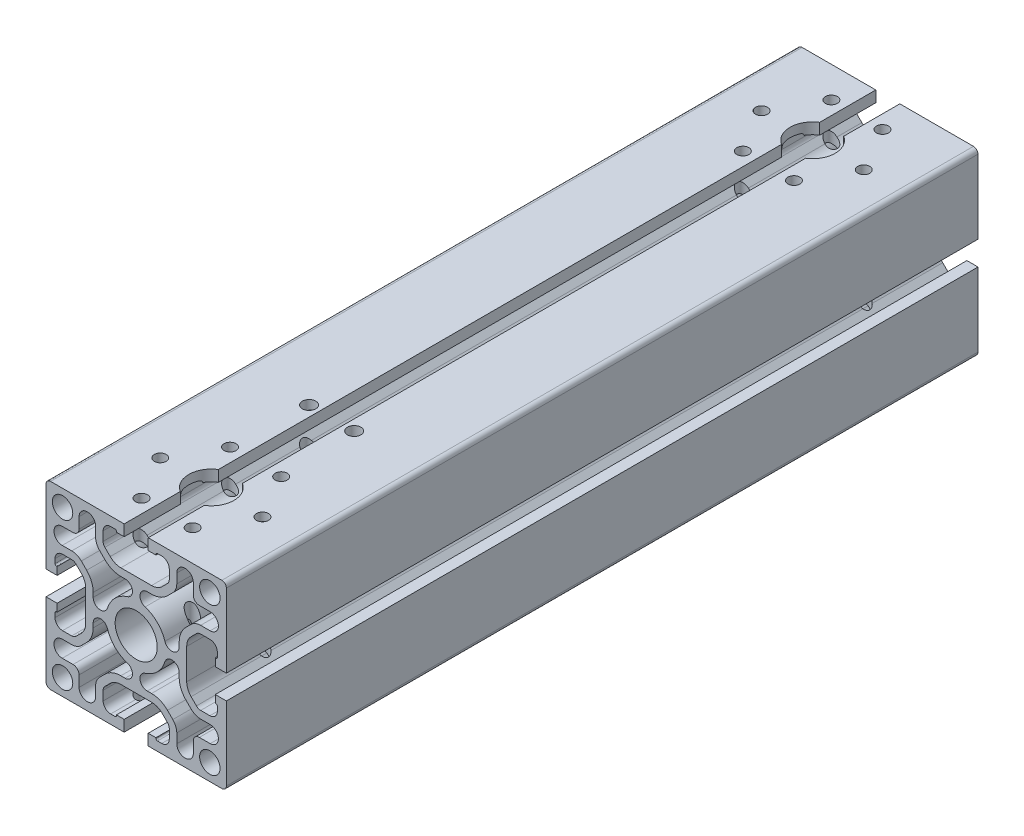
SolidWorks part; units mm, degrees
ref_plane "Płaszczyzna przednia" through (0, 0, 0) normal (0, 0, 1) x (1, 0, 0)
ref_plane "Płaszczyzna górna" through (0, 0, 0) normal (0, 1, 0) x (1, 0, 0)
ref_plane "Płaszczyzna prawa" through (0, 0, 0) normal (1, 0, 0) x (0, 0, -1)
ref_plane "Plane1" through (0, 0, 0) normal (0, 0, -1) x (-1, 0, 0)
sketch "Sketch1" plane through (0, 0, 0) normal (0, 0, -1) x (-1, 0, 0)
  line L0 (5.1034, -14.3) -> (3.6784, -14.3)
  line L1 (14.3, -3.6784) -> (14.3, -5.1134)
  line L2 (16.4818, -10.4017) -> (18.2431, -12.173)
  line L3 (21.434, -13.5) -> (24.6, -13.5)
  line L4 (24.6, -19) -> (21, -19)
  line L5 (19, -21) -> (19, -24.6)
  line L6 (13.5, -24.6) -> (13.5, -21.454)
  line L7 (12.182, -18.272) -> (10.4067, -16.4967)
  line L8 (-3.6784, -14.3) -> (-5.1034, -14.3)
  line L9 (-10.4067, -16.4967) -> (-12.182, -18.272)
  line L10 (-13.5, -21.454) -> (-13.5, -24.6)
  line L11 (-19, -24.6) -> (-19, -21)
  line L12 (-21, -19) -> (-24.6, -19)
  line L13 (-24.6, -13.5) -> (-21.434, -13.5)
  line L14 (-18.2431, -12.173) -> (-16.4818, -10.4017)
  line L15 (-14.3, -5.1134) -> (-14.3, -3.6784)
  line L16 (-5.1034, 14.3) -> (-3.6784, 14.3)
  line L17 (-14.3, 3.6784) -> (-14.3, 5.1134)
  line L18 (-16.4818, 10.4017) -> (-18.2431, 12.173)
  line L19 (-21.434, 13.5) -> (-24.6, 13.5)
  line L20 (-24.6, 19) -> (-21, 19)
  line L21 (-19, 21) -> (-19, 24.6)
  line L22 (-13.5, 24.6) -> (-13.5, 21.454)
  line L23 (-12.182, 18.272) -> (-10.4067, 16.4967)
  line L24 (3.6784, 14.3) -> (5.1034, 14.3)
  line L25 (10.4067, 16.4967) -> (12.182, 18.272)
  line L26 (13.5, 21.454) -> (13.5, 24.6)
  line L27 (19, 24.6) -> (19, 21)
  line L28 (21, 19) -> (24.6, 19)
  line L29 (24.6, 13.5) -> (21.434, 13.5)
  line L30 (18.2431, 12.173) -> (16.4818, 10.4017)
  line L31 (14.3, 5.1134) -> (14.3, 3.6784)
  line L32 (5.1, 16.8) -> (-5.11, 16.8)
  line L33 (-8.6455, 18.2645) -> (-10.42, 20.04)
  line L34 (-11, 21.45) -> (-11, 24.5)
  line L35 (-8.5, 27) -> (-7.07, 27)
  line L36 (-6.57, 26.5) -> (-6.57, 26.3)
  line L37 (-6.57, 26.3) -> (-4, 26.3)
  line L38 (-4, 26.3) -> (-4, 30)
  line L39 (-4, 30) -> (-28.5, 30)
  line L40 (-30, 28.5) -> (-30, 4)
  line L41 (-30, 4) -> (-26.3, 4)
  line L42 (-26.3, 4) -> (-26.3, 6.57)
  line L43 (-26.3, 6.57) -> (-26.5, 6.57)
  line L44 (-27, 7.07) -> (-27, 8.5)
  line L45 (-24.5, 11) -> (-21.45, 11)
  line L46 (-20.0358, 10.4142) -> (-18.27, 8.65)
  line L47 (-16.8, 5.11) -> (-16.8, -5.1)
  line L48 (-18.2645, -8.6355) -> (-20.04, -10.41)
  line L49 (-21.45, -11) -> (-24.5, -11)
  line L50 (-27, -8.5) -> (-27, -7.07)
  line L51 (-26.5, -6.57) -> (-26.3, -6.57)
  line L52 (-26.3, -6.57) -> (-26.3, -4)
  line L53 (-26.3, -4) -> (-30, -4)
  line L54 (-30, -4) -> (-30, -28.5)
  line L55 (-28.5, -30) -> (-4, -30)
  line L56 (-4, -30) -> (-4, -26.3)
  line L57 (-4, -26.3) -> (-6.57, -26.3)
  line L58 (-6.57, -26.3) -> (-6.57, -26.5)
  line L59 (-7.07, -27) -> (-8.5, -27)
  line L60 (-11, -24.5) -> (-11, -21.45)
  line L61 (-10.4142, -20.0358) -> (-8.65, -18.26)
  line L62 (-5.11, -16.8) -> (5.1, -16.8)
  line L63 (8.64, -18.26) -> (10.41, -20.03)
  line L64 (11, -21.45) -> (11, -24.5)
  line L65 (8.5, -27) -> (7.07, -27)
  line L66 (6.57, -26.5) -> (6.57, -26.3)
  line L67 (6.57, -26.3) -> (4, -26.3)
  line L68 (4, -26.3) -> (4, -30)
  line L69 (4, -30) -> (28.5, -30)
  line L70 (30, -28.5) -> (30, -4)
  line L71 (30, -4) -> (26.3, -4)
  line L72 (26.3, -4) -> (26.3, -6.57)
  line L73 (26.3, -6.57) -> (26.5, -6.57)
  line L74 (27, -7.07) -> (27, -8.5)
  line L75 (24.5, -11) -> (21.45, -11)
  line L76 (20.0358, -10.4142) -> (18.26, -8.64)
  line L77 (16.8, -5.1) -> (16.8, 5.11)
  line L78 (18.26, 8.65) -> (20.0358, 10.4142)
  line L79 (21.45, 11) -> (24.5, 11)
  line L80 (27, 8.5) -> (27, 7.07)
  line L81 (26.5, 6.57) -> (26.3, 6.57)
  line L82 (26.3, 6.57) -> (26.3, 4)
  line L83 (26.3, 4) -> (30, 4)
  line L84 (30, 4) -> (30, 28.5)
  line L85 (28.5, 30) -> (4, 30)
  line L86 (4, 30) -> (4, 26.3)
  line L87 (4, 26.3) -> (6.57, 26.3)
  line L88 (6.57, 26.3) -> (6.57, 26.5)
  line L89 (7.07, 27) -> (8.5, 27)
  line L90 (11, 24.5) -> (11, 21.45)
  line L91 (10.4142, 20.0358) -> (8.64, 18.27)
  circle A0 centre (-24.5, 24.5) radius 3.4
  circle A1 centre (24.5, 24.5) radius 3.4
  circle A2 centre (-24.5, -24.49) radius 3.4
  circle A3 centre (24.5, -24.49) radius 3.4
  circle A4 centre (0, 0) radius 7
  arc A5 (3.6784, -14.3) -> (2.9597, -9.552) centre (3.6784, -11.8716) cw
  arc A6 (2.9597, -9.552) -> (9.552, -2.9597) centre (0, 0) ccw
  arc A7 (9.552, -2.9597) -> (14.3, -3.6784) centre (11.8716, -3.6784) cw
  arc A8 (14.3, -5.1134) -> (16.4818, -10.4017) centre (21.8, -5.1134) ccw
  arc A9 (18.2431, -12.173) -> (21.434, -13.5) centre (21.434, -9) ccw
  arc A10 (24.6, -13.5) -> (24.6, -19) centre (24.6, -16.25) cw
  arc A11 (21, -19) -> (19, -21) centre (21, -21) ccw
  arc A12 (19, -24.6) -> (13.5, -24.6) centre (16.25, -24.6) cw
  arc A13 (13.5, -21.454) -> (12.182, -18.272) centre (9, -21.454) ccw
  arc A14 (10.4067, -16.4967) -> (5.1034, -14.3) centre (5.1034, -21.8) ccw
  arc A15 (-9.552, -2.9597) -> (-2.9597, -9.552) centre (0, 0) ccw
  arc A16 (-2.9597, -9.552) -> (-3.6784, -14.3) centre (-3.6784, -11.8716) cw
  arc A17 (-5.1034, -14.3) -> (-10.4067, -16.4967) centre (-5.1034, -21.8) ccw
  arc A18 (-12.182, -18.272) -> (-13.5, -21.454) centre (-9, -21.454) ccw
  arc A19 (-13.5, -24.6) -> (-19, -24.6) centre (-16.25, -24.6) cw
  arc A20 (-19, -21) -> (-21, -19) centre (-21, -21) ccw
  arc A21 (-24.6, -19) -> (-24.6, -13.5) centre (-24.6, -16.25) cw
  arc A22 (-21.434, -13.5) -> (-18.2431, -12.173) centre (-21.434, -9) ccw
  arc A23 (-16.4818, -10.4017) -> (-14.3, -5.1134) centre (-21.8, -5.1134) ccw
  arc A24 (-14.3, -3.6784) -> (-9.552, -2.9597) centre (-11.8716, -3.6784) cw
  arc A25 (-3.6784, 14.3) -> (-2.9597, 9.552) centre (-3.6784, 11.8716) cw
  arc A26 (-2.9597, 9.552) -> (-9.552, 2.9597) centre (0, 0) ccw
  arc A27 (-9.552, 2.9597) -> (-14.3, 3.6784) centre (-11.8716, 3.6784) cw
  arc A28 (-14.3, 5.1134) -> (-16.4818, 10.4017) centre (-21.8, 5.1134) ccw
  arc A29 (-18.2431, 12.173) -> (-21.434, 13.5) centre (-21.434, 9) ccw
  arc A30 (-24.6, 13.5) -> (-24.6, 19) centre (-24.6, 16.25) cw
  arc A31 (-21, 19) -> (-19, 21) centre (-21, 21) ccw
  arc A32 (-19, 24.6) -> (-13.5, 24.6) centre (-16.25, 24.6) cw
  arc A33 (-13.5, 21.454) -> (-12.182, 18.272) centre (-9, 21.454) ccw
  arc A34 (-10.4067, 16.4967) -> (-5.1034, 14.3) centre (-5.1034, 21.8) ccw
  arc A35 (9.552, 2.9597) -> (2.9597, 9.552) centre (0, 0) ccw
  arc A36 (2.9597, 9.552) -> (3.6784, 14.3) centre (3.6784, 11.8716) cw
  arc A37 (5.1034, 14.3) -> (10.4067, 16.4967) centre (5.1034, 21.8) ccw
  arc A38 (12.182, 18.272) -> (13.5, 21.454) centre (9, 21.454) ccw
  arc A39 (13.5, 24.6) -> (19, 24.6) centre (16.25, 24.6) cw
  arc A40 (19, 21) -> (21, 19) centre (21, 21) ccw
  arc A41 (24.6, 19) -> (24.6, 13.5) centre (24.6, 16.25) cw
  arc A42 (21.434, 13.5) -> (18.2431, 12.173) centre (21.434, 9) ccw
  arc A43 (16.4818, 10.4017) -> (14.3, 5.1134) centre (21.8, 5.1134) ccw
  arc A44 (14.3, 3.6784) -> (9.552, 2.9597) centre (11.8716, 3.6784) cw
  arc A45 (-5.11, 16.8) -> (-8.6455, 18.2645) centre (-5.11, 21.8) cw
  arc A46 (-10.42, 20.04) -> (-11, 21.45) centre (-8.9925, 21.4515) cw
  arc A47 (-11, 24.5) -> (-8.5, 27) centre (-8.5, 24.5) cw
  arc A48 (-7.07, 27) -> (-6.57, 26.5) centre (-7.07, 26.5) cw
  arc A49 (-28.5, 30) -> (-30, 28.5) centre (-28.5, 28.5) ccw
  arc A50 (-26.5, 6.57) -> (-27, 7.07) centre (-26.5, 7.07) cw
  arc A51 (-27, 8.5) -> (-24.5, 11) centre (-24.5, 8.5) cw
  arc A52 (-21.45, 11) -> (-20.0358, 10.4142) centre (-21.45, 9) cw
  arc A53 (-18.27, 8.65) -> (-16.8, 5.11) centre (-21.7951, 5.111) cw
  arc A54 (-16.8, -5.1) -> (-18.2645, -8.6355) centre (-21.8, -5.1) cw
  arc A55 (-20.04, -10.41) -> (-21.45, -11) centre (-21.4424, -9.0384) cw
  arc A56 (-24.5, -11) -> (-27, -8.5) centre (-24.5, -8.5) cw
  arc A57 (-27, -7.07) -> (-26.5, -6.57) centre (-26.5, -7.07) cw
  arc A58 (-30, -28.5) -> (-28.5, -30) centre (-28.5, -28.5) ccw
  arc A59 (-6.57, -26.5) -> (-7.07, -27) centre (-7.07, -26.5) cw
  arc A60 (-8.5, -27) -> (-11, -24.5) centre (-8.5, -24.5) cw
  arc A61 (-11, -21.45) -> (-10.4142, -20.0358) centre (-9, -21.45) cw
  arc A62 (-8.65, -18.26) -> (-5.11, -16.8) centre (-5.1017, -21.8418) cw
  arc A63 (5.1, -16.8) -> (8.64, -18.26) centre (5.0917, -21.8418) cw
  arc A64 (10.41, -20.03) -> (11, -21.45) centre (8.9927, -21.4515) cw
  arc A65 (11, -24.5) -> (8.5, -27) centre (8.5, -24.5) cw
  arc A66 (7.07, -27) -> (6.57, -26.5) centre (7.07, -26.5) cw
  arc A67 (28.5, -30) -> (30, -28.5) centre (28.5, -28.5) ccw
  arc A68 (26.5, -6.57) -> (27, -7.07) centre (26.5, -7.07) cw
  arc A69 (27, -8.5) -> (24.5, -11) centre (24.5, -8.5) cw
  arc A70 (21.45, -11) -> (20.0358, -10.4142) centre (21.45, -9) cw
  arc A71 (18.26, -8.64) -> (16.8, -5.1) centre (21.8418, -5.0917) cw
  arc A72 (16.8, 5.11) -> (18.26, 8.65) centre (21.8418, 5.1017) cw
  arc A73 (20.0358, 10.4142) -> (21.45, 11) centre (21.45, 9) cw
  arc A74 (24.5, 11) -> (27, 8.5) centre (24.5, 8.5) cw
  arc A75 (27, 7.07) -> (26.5, 6.57) centre (26.5, 7.07) cw
  arc A76 (30, 28.5) -> (28.5, 30) centre (28.5, 28.5) ccw
  arc A77 (6.57, 26.5) -> (7.07, 27) centre (7.0699, 26.5001) cw
  arc A78 (8.5, 27) -> (11, 24.5) centre (8.5, 24.5) cw
  arc A79 (11, 21.45) -> (10.4142, 20.0358) centre (9, 21.45) cw
  arc A80 (8.64, 18.27) -> (5.1, 16.8) centre (5.101, 21.7951) cw
extrude "Boss-Extrude1" add sketch "Sketch1" against normal blind 250
sketch "Sketch2" plane through (0, 0, 0) normal (0, 1, 0) x (1, 0, 0)
  line L0 (4, -250) -> (28.5, -250) construction
  line L1 (-28.5, 0) -> (-4, 0) construction
  line L2 (-30, -250) -> (-30, 0) construction
  circle A0 centre (0, -25) radius 7.5
  circle A1 centre (0, -225) radius 7.5
  dimension "D5" = 15
  dimension "D6" = 15
  dimension "D1" = 25
  dimension "D2" = 25
  dimension "D3" = 30
  dimension "D4" = 30
extrude "Cut-Extrude1" cut sketch "Sketch2" along normal through all both and the other way through all
sketch "Sketch3" plane through (0, 0, 0) normal (0, 1, 0) x (1, 0, 0)
  line L0 (30, -125) -> (-77.9653, -125) construction
  line L2 (0, -194.5) -> (0, -175.5) construction
  line L3 (7.5, -185) -> (-7.5, -185) construction
  line L4 (-28.5, -250) -> (-4, -250) construction
  circle A0 centre (0, -225) radius 17 construction
  circle A1 centre (-17, -225) radius 2
  circle A2 centre (-8.5, -210.2776) radius 2
  circle A3 centre (8.5, -210.2776) radius 2
  circle A4 centre (17, -225) radius 2
  circle A5 centre (8.5, -239.7224) radius 2
  circle A6 centre (-8.5, -239.7224) radius 2
  circle A7 centre (0, -25) radius 17 construction
  circle A8 centre (-8.5, -10.2776) radius 2
  circle A9 centre (8.5, -10.2776) radius 2
  circle A10 centre (17, -25) radius 2
  circle A11 centre (8.5, -39.7224) radius 2
  circle A12 centre (-8.5, -39.7224) radius 2
  circle A13 centre (-17, -25) radius 2
  circle A14 centre (0, -194.5) radius 2.2345
  circle A15 centre (-7.5, -185) radius 2.2345
  circle A16 centre (0, -175.5) radius 2.2345
  circle A17 centre (7.5, -185) radius 2.2345
  point P18 (0, -225)
  point P32 (0, -25)
  dimension "D1" = 34
  dimension "D2" = 4
  dimension "D4" = 15
  dimension "D5" = 7.5
  dimension "D6" = 19
  dimension "D7" = 9.5
  dimension "D8" = 65
  dimension "D3" = 6
extrude "Cut-Extrude2" cut sketch "Sketch3" along normal through all both and the other way through all
